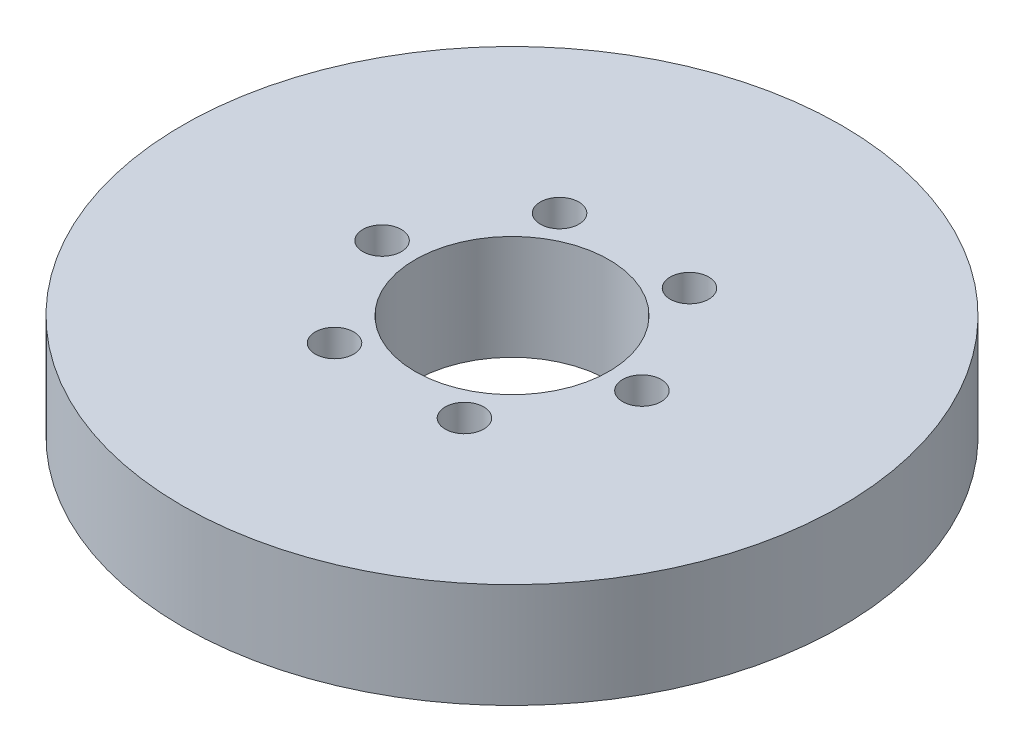
SolidWorks part; units mm, degrees
ref_plane "Front Plane" through (0, 0, 0) normal (0, 0, 1) x (1, 0, 0)
ref_plane "Top Plane" through (0, 0, 0) normal (0, 1, 0) x (1, 0, 0)
ref_plane "Right Plane" through (0, 0, 0) normal (1, 0, 0) x (0, 0, -1)
sketch "Sketch1" plane through (0, 0, 0) normal (0, 1, 0) x (1, 0, 0)
  circle A0 centre (0, 0) radius 85
  dimension "FLANGE_OD" = 170
extrude "Boss-Extrude1" add sketch "Sketch1" along normal blind 27
sketch "Sketch2" plane through (0, 0, 0) normal (0, 1, 0) x (1, 0, 0)
  circle A0 centre (0, 0) radius 25
  dimension "BORE_D" = 50
extrude "Cut-Extrude1" cut sketch "Sketch2" along normal through all
sketch "Sketch3" plane through (0, 27, 0) normal (0, 1, 0) x (1, 0, 0)
  circle A0 centre (0, 0) radius 33.5101 construction
  circle A1 centre (-33.5101, 0) radius 4.9738
  dimension "BOLT_D" = 9.9475
  dimension "BOLT_PCD" = 67.0202
extrude "Cut-Extrude2" cut sketch "Sketch3" against normal blind 23.2024
pattern_circular "CirPattern1" count 6 over 360 about axis through (0, 0, 0) along (0, 1, 0) of "Cut-Extrude2"
